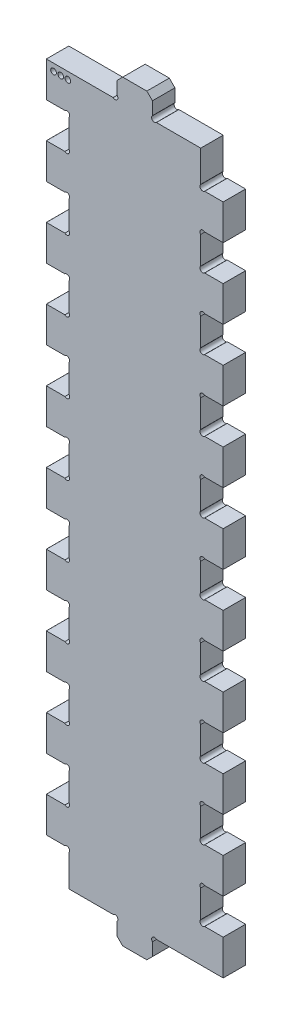
SolidWorks part; units mm, degrees
material "PVC Rigid"
ref_plane "Front Plane" through (0, 0, 0) normal (0, 0, 1) x (1, 0, 0)
ref_plane "Top Plane" through (0, 0, 0) normal (0, 1, 0) x (1, 0, 0)
ref_plane "Right Plane" through (0, 0, 0) normal (1, 0, 0) x (0, 0, -1)
sketch "Model" [suppressed]
  dimension "D3" = 0.7937
  dimension "D1" = 10
  dimension "D2" = 10
sketch "Sketch1" plane through (0, 0, 0) normal (0, 0, 1) x (1, 0, 0)
  line L1 (0, 0) -> (50, 0)
  line L2 (0, 0) -> (0, 200.0001)
  line L3 (0, 200.0001) -> (50, 200.0001)
  line L4 (50, 0) -> (50, 200.0001)
  dimension "D1" = 200.0001
  dimension "D2" = 50
extrude "Boss-Extrude1" add sketch "Sketch1" along normal blind 6.35
sketch "Sketch2" plane through (0, 0, 0) normal (0, 0, 1) x (1, 0, 0)
  line L0 (0, 100.0001) -> (50, 100.0001) construction
  line L1 (50, 200.0001) -> (0, 200.0001) construction
  line L2 (25, 200.0001) -> (25, 203.1751) construction
  line L3 (20, 206.3501) -> (30, 206.3501)
  line L4 (20, 206.3501) -> (20, 200.0001)
  line L5 (20, 200.0001) -> (30, 200.0001)
  line L6 (30, 206.3501) -> (30, 200.0001)
  line L7 (20, 206.3501) -> (30, 200.0001) construction
  line L8 (20, 200.0001) -> (30, 206.3501) construction
  line L9 (0, 200.0001) -> (0, 0) construction
  line L10 (50, 0) -> (50, 200.0001) construction
  line L11 (20, 0) -> (30, -6.35) construction
  line L12 (20, -6.35) -> (30, 0) construction
  line L13 (25, 0) -> (25, -3.175) construction
  line L14 (30, -6.35) -> (30, 0)
  line L15 (20, 0) -> (30, 0)
  line L16 (20, -6.35) -> (20, 0)
  line L17 (20, -6.35) -> (30, -6.35)
  dimension "D1" = 6.35
  dimension "D2" = 10
extrude "Boss-Extrude2" add sketch "Sketch2" along normal blind 6.35
sketch "Sketch3" plane through (0, 0, 6.35) normal (0, 0, 1) x (1, 0, 0)
  line L0 (25, 206.3501) -> (25, -6.35) construction
  line L1 (30, 206.3501) -> (20, 206.3501) construction
  line L2 (20, -6.35) -> (30, -6.35) construction
  line L3 (6.35, 200.0001) -> (6.35, 0) construction
  line L4 (20, 200.0001) -> (0, 200.0001) construction
  line L5 (0, 0) -> (20, 0) construction
  line L6 (0, 200.0001) -> (0, 0) construction
  line L7 (6.35, 0) -> (0, 0)
  line L8 (6.35, 0) -> (6.35, 10)
  line L9 (6.35, 10) -> (0, 10)
  line L10 (0, 0) -> (0, 10)
  line L11 (50, 0) -> (50, 10)
  line L12 (43.65, 10) -> (50, 10)
  line L13 (43.65, 0) -> (43.65, 10)
  line L14 (43.65, 0) -> (50, 0)
  dimension "D1" = 6.35
  dimension "D2" = 10
extrude "Cut-Extrude1" [suppressed] cut sketch "Sketch3" against normal blind 6.35
pattern_linear "LPattern2" [suppressed] count 10 spacing 20 of bodies 108
sketch "Sketch4" [suppressed] plane through (0, 0, 6.35) normal (0, 0, 1) x (1, 0, 0)
  line L0 (0, 10) -> (6.35, 0) construction
  line L1 (6.35, 10) -> (5.2275, 10) construction
  line L2 (0.5613, 0.5613) -> (5.7887, 0.5613) construction
  line L3 (0.5613, 0.5613) -> (0.5613, 9.4387) construction
  line L4 (0.5613, 9.4387) -> (5.7887, 9.4387) construction
  line L5 (5.7887, 0.5613) -> (5.7887, 9.4387) construction
  line L6 (0.5613, 0.5613) -> (5.7887, 9.4387) construction
  line L7 (0.5613, 9.4387) -> (5.7887, 0.5613) construction
  line L8 (6.35, 10) -> (0, 10) construction
  line L9 (6.35, 10) -> (6.35, 8.8775) construction
  line L10 (6.35, 0) -> (6.35, 10) construction
  line L11 (25, 206.3501) -> (25, -6.35) construction
  line L12 (30, 206.3501) -> (20, 206.3501) construction
  line L13 (20, -6.35) -> (30, -6.35) construction
  line L14 (44.2113, 9.4387) -> (44.2113, 20.5613) construction
  line L15 (43.65, 10) -> (43.65, 8.8775) construction
  line L16 (49.4387, 9.4387) -> (44.2113, 0.5613) construction
  line L17 (49.4387, 0.5613) -> (44.2113, 9.4387) construction
  line L18 (44.2113, 0.5613) -> (44.2113, 9.4387) construction
  line L19 (49.4387, 9.4387) -> (44.2113, 9.4387) construction
  line L20 (49.4387, 0.5613) -> (49.4387, 9.4387) construction
  line L21 (49.4387, 0.5613) -> (44.2113, 0.5613) construction
  line L22 (43.65, 10) -> (44.7725, 10) construction
  line L23 (5.7887, 9.4387) -> (5.7887, 20.5613) construction
  line L24 (50, 10) -> (43.65, 0) construction
  circle A0 centre (5.7887, 9.4387) radius 0.7938
  circle A4 centre (5.7887, 20.5613) radius 0.7938
  circle A7 centre (44.2113, 20.5613) radius 0.7937
  circle A8 centre (44.2113, 9.4387) radius 0.7937
  point P4 (3.175, 5)
  point P40 (46.825, 5)
  dimension "D1" = 1.5875
extrude "Cut-Extrude3" [suppressed] cut sketch "Sketch4" against normal blind 6.35
pattern_linear "LPattern3" [suppressed] count 9 spacing 20 of bodies 112
sketch "Sketch8" plane through (0, 0, 6.35) normal (0, 0, 1) x (1, 0, 0)
  line L0 (6.35, 200.0001) -> (6.35, 0) construction
  line L1 (20, 200.0001) -> (0, 200.0001) construction
  line L2 (0, 0) -> (20, 0) construction
  line L3 (0, 200.0001) -> (0, 0) construction
  line L4 (43.65, 200.0001) -> (43.65, 0) construction
  line L5 (0, 0) -> (6.35, 0)
  line L6 (0, 0) -> (0, 10)
  line L7 (0, 10) -> (6.35, 10)
  line L8 (6.35, 0) -> (6.35, 10)
  line L9 (50, 200.0001) -> (30, 200.0001) construction
  line L10 (30, 0) -> (50, 0) construction
  line L11 (50, 0) -> (50, 200.0001) construction
  line L12 (43.65, 10) -> (50, 10)
  line L13 (43.65, 10) -> (43.65, 20)
  line L14 (43.65, 20) -> (50, 20)
  line L15 (50, 10) -> (50, 20)
  dimension "D1" = 6.35
  dimension "D2" = 10
  dimension "D3" = 10
  dimension "D4" = 6.35
  dimension "D5" = 10
extrude "Cut-Extrude6" cut sketch "Sketch8" against normal through all
pattern_linear "LPattern4" count 10 spacing 20 along (0, 1, 0) of "Cut-Extrude6"
sketch "Sketch9" plane through (0, 0, 6.35) normal (0, 0, 1) x (1, 0, 0)
  line L0 (0, 30) -> (6.35, 20) construction
  line L1 (6.35, 30) -> (5.2275, 30) construction
  line L2 (0.5613, 20.5613) -> (5.7887, 20.5613) construction
  line L3 (0.5613, 20.5613) -> (0.5613, 29.4388) construction
  line L4 (0.5613, 29.4388) -> (5.7887, 29.4388) construction
  line L5 (5.7887, 20.5613) -> (5.7887, 29.4388) construction
  line L6 (0.5613, 20.5613) -> (5.7887, 29.4388) construction
  line L7 (0.5613, 29.4388) -> (5.7887, 20.5613) construction
  line L8 (6.35, 30) -> (0, 30) construction
  line L9 (6.35, 30) -> (6.35, 28.8775) construction
  line L10 (6.35, 20) -> (6.35, 30) construction
  line L11 (43.65, 20) -> (50, 10) construction
  line L12 (43.65, 20) -> (44.7725, 20) construction
  line L13 (44.2113, 10.5613) -> (49.4387, 10.5613) construction
  line L14 (44.2113, 10.5613) -> (44.2113, 19.4387) construction
  line L15 (44.2113, 19.4387) -> (49.4387, 19.4387) construction
  line L16 (49.4387, 10.5613) -> (49.4387, 19.4387) construction
  line L17 (44.2113, 10.5613) -> (49.4387, 19.4387) construction
  line L18 (44.2113, 19.4387) -> (49.4387, 10.5613) construction
  line L19 (50, 20) -> (43.65, 20) construction
  line L20 (43.65, 20) -> (43.65, 18.8775) construction
  line L21 (43.65, 20) -> (43.65, 10) construction
  line L22 (50, 20) -> (50, 30) construction
  circle A0 centre (5.7887, 29.4388) radius 0.7938
  circle A1 centre (5.7887, 20.5613) radius 0.7938
  circle A2 centre (44.2113, 19.4387) radius 0.7937
  circle A3 centre (44.2113, 10.5613) radius 0.7937
  point P4 (3.175, 25)
  point P23 (46.825, 15)
  dimension "D1" = 1.5875
  dimension "D2" = 10
extrude "Cut-Extrude7" cut sketch "Sketch9" against normal through all
pattern_linear "LPattern5" count 9 spacing 20 along (0, 1, 0) of "Cut-Extrude7"
sketch "Sketch10" plane through (0, 0, 6.35) normal (0, 0, 1) x (1, 0, 0)
  line L0 (0, 10) -> (6.35, 0) construction
  line L1 (5.2275, 10) -> (6.35, 10) construction
  line L2 (0.5613, 0.5613) -> (5.7887, 0.5613) construction
  line L3 (0.5613, 0.5613) -> (0.5613, 9.4387) construction
  line L4 (0.5613, 9.4387) -> (5.7887, 9.4387) construction
  line L5 (5.7887, 0.5613) -> (5.7887, 9.4387) construction
  line L6 (0.5613, 0.5613) -> (5.7887, 9.4387) construction
  line L7 (0.5613, 9.4387) -> (5.7887, 0.5613) construction
  line L8 (6.35, 10) -> (0, 10) construction
  line L9 (6.35, 10) -> (6.35, 8.8775) construction
  line L10 (6.35, 0) -> (6.35, 10) construction
  line L11 (6.35, 5) -> (3.175, 5) construction
  line L12 (0, 200.0001) -> (50, 0) construction
  line L13 (43.65, 200.0001) -> (50, 190.0001) construction
  line L14 (44.7725, 190.0001) -> (43.65, 190.0001) construction
  line L15 (44.2113, 190.5614) -> (49.4387, 190.5614) construction
  line L16 (44.2113, 190.5614) -> (44.2113, 199.4388) construction
  line L17 (44.2113, 199.4388) -> (49.4387, 199.4388) construction
  line L18 (49.4387, 190.5614) -> (49.4387, 199.4388) construction
  line L19 (44.2113, 190.5614) -> (49.4387, 199.4388) construction
  line L20 (44.2113, 199.4388) -> (49.4387, 190.5614) construction
  line L21 (43.65, 190.0001) -> (50, 190.0001) construction
  line L22 (43.65, 190.0001) -> (43.65, 191.1226) construction
  line L23 (43.65, 200.0001) -> (43.65, 190.0001) construction
  circle A0 centre (5.7887, 9.4387) radius 0.7938
  circle A2 centre (44.2113, 190.5614) radius 0.7937
  point P4 (3.175, 5)
  point P28 (46.825, 195.0001)
  dimension "D1" = 1.5875
  dimension "D2" = 1.5875
extrude "Cut-Extrude8" cut sketch "Sketch10" against normal through all
chamfer "Chamfer1" distance 1.5875 angle 45 4 edges at (30, -6.35, 3.175) (20, -6.35, 3.175) (20, 206.3501, 3.175) (30, 206.3501, 3.175)
sketch "Sketch5" [suppressed] plane through (0, 0, 6.35) normal (0, 0, 1) x (1, 0, 0)
  line L0 (6.35, 180.0001) -> (0, 190.0001) construction
  line L1 (6.35, 190.0001) -> (5.2275, 190.0001) construction
  line L2 (0.5613, 180.5614) -> (5.7887, 180.5614) construction
  line L3 (0.5613, 180.5614) -> (0.5613, 189.4388) construction
  line L4 (0.5613, 189.4388) -> (5.7887, 189.4388) construction
  line L5 (5.7887, 180.5614) -> (5.7887, 189.4388) construction
  line L6 (0.5613, 180.5614) -> (5.7887, 189.4388) construction
  line L7 (0.5613, 189.4388) -> (5.7887, 180.5614) construction
  line L8 (6.35, 190.0001) -> (0, 190.0001) construction
  line L9 (6.35, 190.0001) -> (6.35, 188.8776) construction
  line L10 (6.35, 181.1226) -> (6.35, 190.0001) construction
  line L15 (25, 206.3501) -> (25, -6.35) construction
  line L16 (28.4125, 206.3501) -> (21.5875, 206.3501) construction
  line L17 (21.5875, -6.35) -> (28.4125, -6.35) construction
  line L20 (43.65, 190.0001) -> (43.65, 188.8776) construction
  line L21 (49.4387, 189.4388) -> (44.2113, 180.5614) construction
  line L22 (49.4387, 180.5614) -> (44.2113, 189.4388) construction
  line L23 (44.2113, 180.5614) -> (44.2113, 189.4388) construction
  line L24 (49.4387, 189.4388) -> (44.2113, 189.4388) construction
  line L25 (49.4387, 180.5614) -> (49.4387, 189.4388) construction
  line L26 (49.4387, 180.5614) -> (44.2113, 180.5614) construction
  line L27 (43.65, 190.0001) -> (44.7725, 190.0001) construction
  line L28 (43.65, 180.0001) -> (50, 190.0001) construction
  line L29 (50, 100.0001) -> (0, 100.0001) construction
  arc A0 (5.2275, 180.0001) -> (6.35, 181.1226) centre (5.7887, 180.5614) ccw construction
  circle A1 centre (5.7887, 189.4388) radius 0.7938
  circle A4 centre (44.2113, 189.4388) radius 0.7937
  point P6 (3.175, 185.0001)
  point P51 (46.825, 185.0001)
  point P56 (25, 100.0001)
  dimension "D1" = 1.5875
extrude "Cut-Extrude4" [suppressed] cut sketch "Sketch5" against normal blind 6.35
sketch "Sketch11" plane through (0, 0, 0) normal (0, 0, 1) x (1, 0, 0)
  line L0 (28.4125, 206.3501) -> (21.5875, 206.3501) construction
  line L11 (20, 201.1226) -> (20, 200.0001) construction
  line L13 (20, 200.0001) -> (18.8775, 200.0001) construction
  line L15 (25, 206.3501) -> (25, -6.35) construction
  line L18 (30, 200.0001) -> (31.1225, 200.0001) construction
  line L19 (30, 201.1226) -> (30, 200.0001) construction
  line L29 (50, 100.0001) -> (0, 100.0001) construction
  circle A2 centre (19.4387, 200.5614) radius 0.7937
  circle A3 centre (30.5613, 200.5614) radius 0.7937
  circle A5 centre (19.4387, -0.5613) radius 0.7937
  circle A6 centre (30.5613, -0.5613) radius 0.7937
  point P56 (25, 100.0001)
  dimension "D1" = 1.5875
  dimension "D2" = 19.4387
  dimension "D3" = 100.0001
  dimension "D4" = 200.0001
extrude "Cut-Extrude10" cut sketch "Sketch11" along normal through all
sketch "Sketch6" [suppressed] plane through (0, 0, 6.35) normal (0, 0, 1) x (1, 0, 0)
  line L0 (6.604, 2.032) -> (43.65, 2.032) construction
  line L1 (43.65, 10) -> (43.65, 0) construction
  line L2 (6.35, 0) -> (18.8775, 0) construction
  line L4 (0, 20) -> (0, 10) construction
  text T0 "COL_BIT" font "Consolas" height 3.5
  dimension "D1" = 2.032
  dimension "D2" = 6.604
extrude "Cut-Extrude5" [suppressed] cut sketch "Sketch6" against normal blind 2.54
sketch "Sketch12" plane through (0, 0, 6.35) normal (0, 0, 1) x (1, 0, 0)
  line L0 (6.604, 2.032) -> (40.0372, 2.032) construction
  text T0 "COL_BIT" font "Consolas" height 3.5
  dimension "D1" = 2.032
  dimension "D2" = 6.604
extrude "Cut-Extrude11" [suppressed] cut sketch "Sketch12" against normal blind 2.54
sketch "Sketch13" [suppressed] plane through (0, 0, 6.35) normal (0, 0, 1) x (1, 0, 0)
  line L0 (0, 10) -> (6.35, 0) construction
  line L1 (5.2275, 10) -> (0, 10) construction
  line L2 (6.337, -0.0127) -> (0.013, -0.0127)
  line L3 (6.337, -0.0127) -> (6.337, 10.0127)
  line L4 (6.337, 10.0127) -> (0.013, 10.0127)
  line L5 (0.013, -0.0127) -> (0.013, 10.0127)
  line L6 (6.337, -0.0127) -> (0.013, 10.0127) construction
  line L7 (6.337, 10.0127) -> (0.013, -0.0127) construction
  line L8 (25, 206.3501) -> (25, -6.35) construction
  line L9 (28.4125, 206.3501) -> (21.5875, 206.3501) construction
  line L10 (21.5875, -6.35) -> (28.4125, -6.35) construction
  line L11 (43.663, 10.0127) -> (49.987, -0.0127) construction
  line L12 (43.663, -0.0127) -> (49.987, 10.0127) construction
  line L13 (50, 10) -> (43.65, 0) construction
  line L14 (49.987, -0.0127) -> (49.987, 10.0127)
  line L15 (43.663, 10.0127) -> (49.987, 10.0127)
  line L16 (43.663, -0.0127) -> (43.663, 10.0127)
  line L17 (43.663, -0.0127) -> (49.987, -0.0127)
  arc A0 (6.35, 8.8775) -> (5.2275, 10) centre (5.7887, 9.4387) ccw construction
  point P4 (3.175, 5)
  point P26 (46.825, 5)
  dimension "D1" = 0.0127
extrude "Cut-Extrude12" [suppressed] cut sketch "Sketch13" against normal through all
pattern_linear "LPattern6" [suppressed] count 10 spacing 20 of bodies 123
sketch "Sketch14" plane through (0, 0, 6.35) normal (0, 0, 1) x (1, 0, 0)
  line L0 (0, 10) -> (6.35, 0) construction
  line L1 (5.2275, 10) -> (0, 10) construction
  line L2 (0.013, -0.0127) -> (6.337, -0.0127)
  line L3 (0.013, -0.0127) -> (0.013, 10.0127)
  line L4 (0.013, 10.0127) -> (6.337, 10.0127)
  line L5 (6.337, -0.0127) -> (6.337, 10.0127)
  line L6 (0.013, -0.0127) -> (6.337, 10.0127) construction
  line L7 (0.013, 10.0127) -> (6.337, -0.0127) construction
  line L8 (43.65, 20) -> (50, 10) construction
  line L9 (50, 20) -> (44.7725, 20) construction
  line L10 (43.663, 9.9873) -> (49.987, 9.9873)
  line L11 (43.663, 9.9873) -> (43.663, 20.0127)
  line L12 (43.663, 20.0127) -> (49.987, 20.0127)
  line L13 (49.987, 9.9873) -> (49.987, 20.0127)
  line L14 (43.663, 9.9873) -> (49.987, 20.0127) construction
  line L15 (43.663, 20.0127) -> (49.987, 9.9873) construction
  arc A0 (6.35, 8.8775) -> (5.2275, 10) centre (5.7887, 9.4387) ccw construction
  arc A1 (44.7725, 20) -> (43.65, 18.8775) centre (44.2113, 19.4387) ccw construction
  point P4 (3.175, 5)
  point P9 (46.825, 15)
  dimension "D1" = 0.0127
  dimension "D2" = 0.0127
extrude "Cut-Extrude13" cut sketch "Sketch14" against normal through all
pattern_linear "LPattern7" count 10 spacing 20 along (0, 1, 0) of "Cut-Extrude13"
sketch "Sketch15" plane through (0, 0, 6.35) normal (0, 0, 1) x (1, 0, 0)
  line L1 (0, 200.0001) -> (2.032, 200.0001) construction
  line L2 (0, 200.0001) -> (0, 197.9681) construction
  line L3 (0, 197.9681) -> (2.032, 197.9681) construction
  line L4 (2.032, 200.0001) -> (2.032, 197.9681) construction
  circle A0 centre (2.032, 197.9681) radius 0.7938
  dimension "D2" = 1.5875
  dimension "D1" = 2.032
extrude "Cut-Extrude14" cut sketch "Sketch15" against normal blind 3.175
pattern_linear "LPattern8" count 3 spacing 2.032 along (1, 0, 0) of "Cut-Extrude14"
equation "\"tHeight\"=0.25"
equation "\"D1@Sketch2\"=\"tHeight\""
equation "\"tWidth\"=0.393701"
equation "\"D2@Sketch2\"=\"tWidth\""
equation "\"D1@Sketch1\"=\"tWidth\"*20"
equation "\"D1@Sketch3\"=\"tHeight\""
equation "\"D2@Sketch3\"=\"tWidth\""
equation "\"D3@LPattern2\"=\"tWidth\"*2"
equation "\"D3@LPattern3\"=\"tWidth\"*2"
equation "\"D1@Sketch8\"=\"tHeight\""
equation "\"D2@Sketch8\"=\"tWidth\""
equation "\"D3@Sketch8\"=\"tWidth\""
equation "\"D4@Sketch8\"=\"tHeight\""
equation "\"D5@Sketch8\"=\"tWidth\""
equation "\"D3@LPattern4\"=\"tWidth\"*2"
equation "\"D3@LPattern5\"=\"tWidth\"*2"
equation "\"D2@Sketch9\"=\"tWidth\""
equation "\"tol\"=0.0005"
equation "\"D1@Sketch13\"=\"tol\""
equation "\"D3@LPattern6\"=\"tWidth\"*2"
equation "\"D1@Sketch14\"=\"tol\""
equation "\"D2@Sketch14\"=\"tol\""
equation "\"version\"= 3"
equation "\"D1@LPattern8\"=\"version\""
